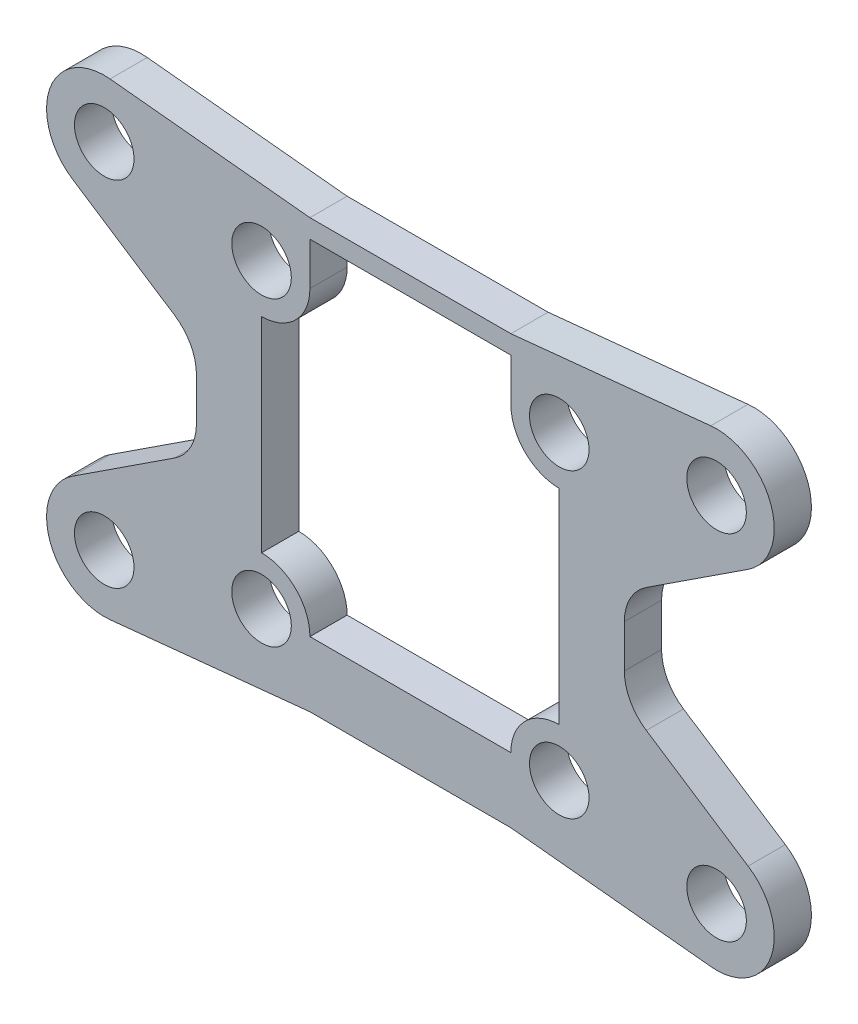
SolidWorks part; units mm, degrees
ref_plane "Front Plane" through (0, 0, 0) normal (0, 0, 1) x (1, 0, 0)
ref_plane "Top Plane" through (0, 0, 0) normal (0, 1, 0) x (1, 0, 0)
ref_plane "Right Plane" through (0, 0, 0) normal (1, 0, 0) x (0, 0, -1)
sketch "Sketch1" plane through (0, 0, 0) normal (0, 0, 1) x (1, 0, 0)
  line L1 (0, 0) -> (23, 0)
  line L2 (0, 0) -> (0, 23)
  line L3 (0, 23) -> (23, 23)
  line L4 (23, 0) -> (23, 23)
  dimension "D1" = 23
  dimension "D2" = 23
extrude "Boss-Extrude1" add sketch "Sketch1" along normal blind 2
fillet "Fillet1" radius 2 4 edges at (23, 23, 1) (23, 0, 1) (0, 0, 1) (0, 23, 1)
sketch "Sketch2" plane through (0, 0, 0) normal (0, 0, 1) x (1, 0, 0)
  line L0 (3.5, 19.7) -> (19.5, 19.7) construction
  line L1 (19.5, 19.7) -> (19.5, 3.5) construction
  line L2 (19.5, 3.5) -> (3.5, 3.5) construction
  line L3 (3.5, 3.5) -> (3.5, 19.7) construction
  line L4 (21, 23) -> (2, 23) construction
  line L5 (23, 2) -> (23, 21) construction
  line L6 (2, 0) -> (21, 0) construction
  line L7 (0, 21) -> (0, 2) construction
  line L8 (3.5, 17.1) -> (3.5, 6.1)
  line L9 (6.1, 3.5) -> (16.9, 3.5)
  line L10 (16.9, 19.7) -> (6.1, 19.7)
  line L11 (19.5, 17.1) -> (19.5, 6.1)
  circle A0 centre (3.5, 19.7) radius 1.6
  circle A1 centre (19.5, 19.7) radius 1.6
  circle A2 centre (19.5, 3.5) radius 1.6
  circle A3 centre (3.5, 3.5) radius 1.6
  arc A4 (6.1, 19.7) -> (3.5, 17.1) centre (3.5, 19.7) cw
  arc A5 (3.5, 6.1) -> (6.1, 3.5) centre (3.5, 3.5) cw
  arc A6 (16.9, 3.5) -> (19.5, 6.1) centre (19.5, 3.5) cw
  arc A7 (16.9, 19.7) -> (19.5, 17.1) centre (19.5, 19.7) ccw
  dimension "D6" = 3.2
  dimension "D7" = 2.6
  dimension "D1" = 3.3
  dimension "D2" = 3.5
  dimension "D3" = 3.5
  dimension "D4" = 3.5
  dimension "D5" = 16
extrude "Cut-Extrude1" cut sketch "Sketch2" along normal blind 2
sketch "Sketch3" plane through (0, 0, 0) normal (0, 0, 1) x (1, 0, 0)
  line L0 (21, 23) -> (2, 23) construction
  line L1 (6.1, 19.7) -> (16.9, 19.7)
  line L2 (6.1, 19.7) -> (6.1, 22)
  line L3 (6.1, 22) -> (16.9, 22)
  line L4 (16.9, 19.7) -> (16.9, 22)
  dimension "D1" = 1
extrude "Cut-Extrude2" cut sketch "Sketch3" along normal blind 2
sketch "Sketch4" plane through (0, 0, 0) normal (0, 0, 1) x (1, 0, 0)
  line L0 (0, 21) -> (0, 2) construction
  line L2 (2, 0) -> (21, 0) construction
  circle A0 centre (11.5, 11.5) radius 14.15 construction
  point P0 (11.5, 11.5)
  point P3 (0, 11.5)
  point P6 (11.5, 0)
  dimension "D1" = 28.3
sketch "Sketch5" plane through (0, 0, 0) normal (0, 0, 1) x (1, 0, 0)
  line L0 (11.5, 11.5) -> (-4.9545, 21) construction
  line L3 (6.1, 23) -> (-6.9654, 24.3187) construction
  line L4 (16.9, 23) -> (21.7765, 21.562)
  line L9 (11.5, 30.5) -> (11.5, -7.5) construction
  line L18 (-7.5, 11.5) -> (30.5, 11.5) construction
  line L40 (21, 23) -> (2, 23) construction
  line L41 (0, 14.0562) -> (-8.8778, 19.8615) construction
  line L42 (0, 21) -> (0, 2) construction
  line L43 (-4.6432, 24.0843) -> (6.1, 23)
  line L44 (6.1, 23) -> (1.2235, 21.562)
  line L45 (1.2235, 21.562) -> (0, 12.6481)
  line L46 (-1.1786, 14.8269) -> (-6.6511, 18.4055)
  line L47 (27.6432, 24.0843) -> (16.9, 23)
  line L48 (24.1786, 14.8269) -> (29.6511, 18.4055)
  line L49 (21.7765, 21.562) -> (23, 12.6481)
  line L50 (16.9, 0) -> (21.7765, 1.438)
  line L51 (27.6432, -1.0843) -> (16.9, 0)
  line L52 (24.1786, 8.1731) -> (29.6511, 4.5945)
  line L53 (21.7765, 1.438) -> (23, 10.3519)
  line L54 (6.1, 0) -> (1.2235, 1.438)
  line L55 (-4.6432, -1.0843) -> (6.1, 0)
  line L56 (-1.1786, 8.1731) -> (-6.6511, 4.5945)
  line L57 (1.2235, 1.438) -> (0, 10.3519)
  circle A0 centre (11.5, 11.5) radius 19 construction
  circle A36 centre (-4.9545, 21) radius 1.6
  circle A37 centre (-4.9545, 21) radius 3.1 construction
  circle A38 centre (-2.6033, 12.6481) radius 2.6033 construction
  circle A39 centre (11.5, 11.5) radius 14.15 construction
  arc A40 (0, 12.6481) -> (-1.1786, 14.8269) centre (-2.6033, 12.6481) ccw
  arc A41 (-4.6432, 24.0843) -> (-6.6511, 18.4055) centre (-4.9545, 21) ccw
  circle A42 centre (27.9545, 21) radius 1.6
  arc A43 (27.6432, 24.0843) -> (29.6511, 18.4055) centre (27.9545, 21) cw
  arc A44 (23, 12.6481) -> (24.1786, 14.8269) centre (25.6033, 12.6481) cw
  circle A45 centre (27.9545, 2) radius 1.6
  arc A46 (27.6432, -1.0843) -> (29.6511, 4.5945) centre (27.9545, 2) ccw
  arc A47 (23, 10.3519) -> (24.1786, 8.1731) centre (25.6033, 10.3519) ccw
  circle A48 centre (-4.9545, 2) radius 1.6
  arc A49 (-4.6432, -1.0843) -> (-6.6511, 4.5945) centre (-4.9545, 2) cw
  arc A50 (0, 10.3519) -> (-1.1786, 8.1731) centre (-2.6033, 10.3519) cw
  point P62 (11.5, 11.5)
  dimension "D1" = 38
  dimension "D2" = 3.2
  dimension "D3" = 6.2
  dimension "D4" = 60
extrude "Boss-Extrude2" add sketch "Sketch5" along normal blind 2 from surface separate body starting at face at (21.1, 19.7, 0)
combine bodies "Combine1" operation type add bodies to combine 118 103 115 116 117
